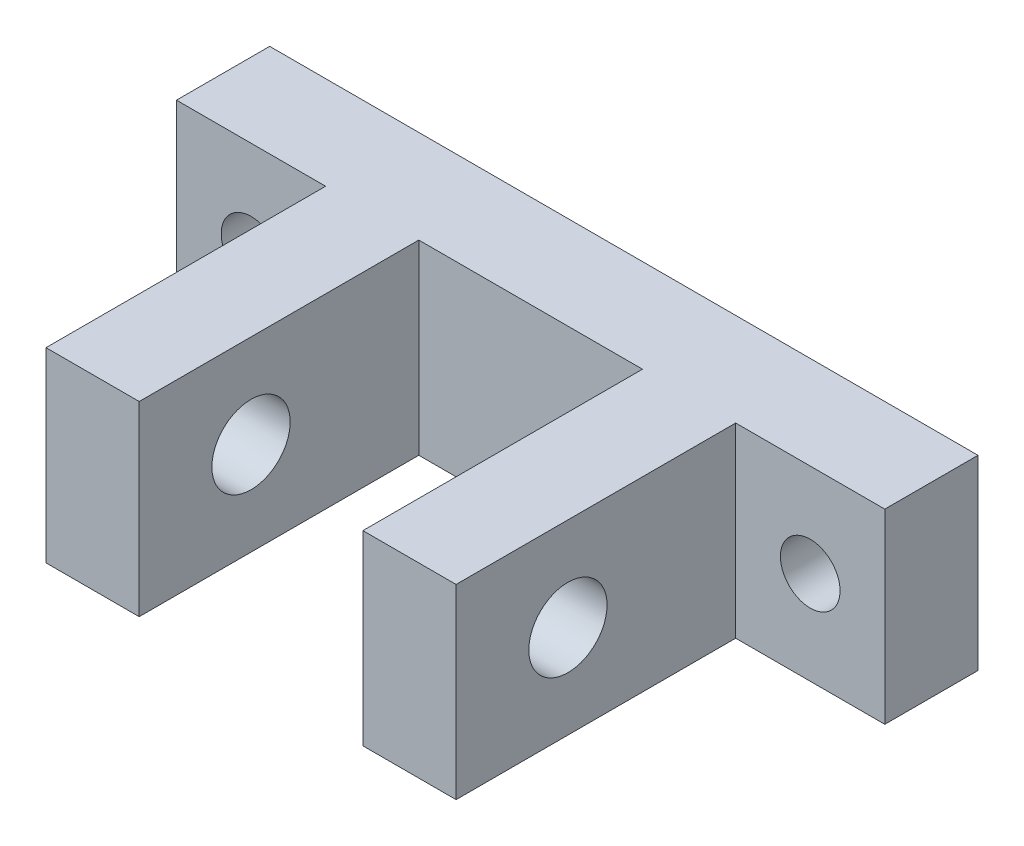
SolidWorks part; units mm, degrees
ref_plane "Front Plane" through (0, 0, 0) normal (0, 0, 1) x (1, 0, 0)
ref_plane "Top Plane" through (0, 0, 0) normal (0, 1, 0) x (1, 0, 0)
ref_plane "Right Plane" through (0, 0, 0) normal (1, 0, 0) x (0, 0, -1)
sketch "Sketch1" plane through (0, 0, 0) normal (0, 1, 0) x (1, 0, 0)
  line L0 (0, 0) -> (0, -20.0709) construction
  line L1 (-11, 0) -> (11, 0)
  line L2 (11, 0) -> (11, -20)
  line L3 (11, -20) -> (6, -20)
  line L4 (6, -20) -> (6, -5)
  line L5 (6, -5) -> (-6, -5)
  line L6 (-6, -20) -> (-6, -5)
  line L7 (-11, -20) -> (-6, -20)
  line L8 (-11, 0) -> (-11, -20)
  line L9 (6, -20) -> (6, -5)
  point P9 (0, -5)
  dimension "D1" = 6
  dimension "D2" = 5
  dimension "D3" = 15
  dimension "D4" = 5
extrude "Boss-Extrude1" add sketch "Sketch1" along normal blind 10 contours L1 L0 L5 L4 L3 L2 | L0 L1 L8 L7 L6 L5 region at (7.2308, 0, 8.2692) region at (-7.2308, 0, 8.2692)
sketch "Sketch2" plane through (11, 0, 0) normal (1, 0, 0) x (0, 0, -1)
  line L0 (-20, 5) -> (0, 5) construction
  line L1 (-20, 10) -> (-20, 0) construction
  line L2 (0, 10) -> (0, 0) construction
  circle A0 centre (-14, 5) radius 2.1
  dimension "D1" = 4.2
  dimension "D2" = 14
extrude "Cut-Extrude1" cut sketch "Sketch2" against normal through all contours A0
sketch "Sketch3" plane through (0, 10, 0) normal (0, 1, 0) x (1, 0, 0)
  line L1 (-19, -5) -> (19, -5)
  line L2 (0, 0) -> (0, -5) construction
  line L3 (-19, 0) -> (19, 0)
  line L4 (19, -5) -> (19, 0)
  line L5 (-11, 0) -> (11, 0) construction
  line L6 (11, 0) -> (11, -20) construction
  line L7 (-19, -5) -> (-19, 0)
  line L8 (6, -5) -> (-6, -5) construction
  dimension "D1" = 8
extrude "Boss-Extrude2" add sketch "Sketch3" against normal through all
sketch "Sketch4" plane through (0, 0, 5) normal (0, 0, 1) x (1, 0, 0)
  line L0 (-19, 5) -> (-11, 5) construction
  line L1 (-19, 0) -> (-19, 10) construction
  line L2 (-11, 10) -> (-11, 0) construction
  line L3 (-15, 0) -> (-15, 10) construction
  line L4 (-19, 0) -> (-11, 0) construction
  line L5 (-19, 10) -> (-11, 10) construction
  line L6 (0, 0) -> (0, 10) construction
  line L7 (6, 0) -> (-6, 0) construction
  line L8 (6, 10) -> (-6, 10) construction
  line L9 (15, 0) -> (15, 10) construction
  line L10 (19, 5) -> (11, 5) construction
  line L11 (-15, 0) -> (-15, 10) construction
  circle A0 centre (-15, 5) radius 1.6
  circle A1 centre (15, 5) radius 1.6
  dimension "D1" = 3.2
extrude "Cut-Extrude2" cut sketch "Sketch4" against normal through all
